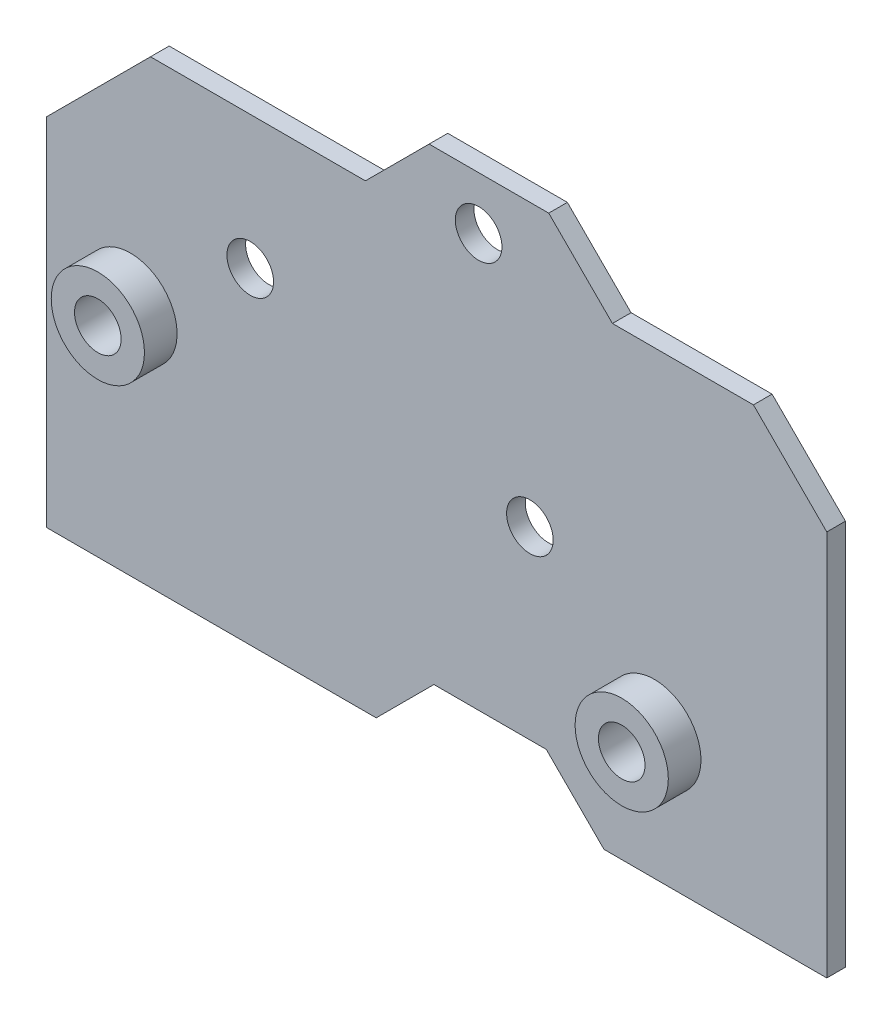
SolidWorks part; units mm, degrees
ref_plane "정면" through (0, 0, 0) normal (0, 0, 1) x (1, 0, 0)
ref_plane "윗면" through (0, 0, 0) normal (0, 1, 0) x (1, 0, 0)
ref_plane "우측면" through (0, 0, 0) normal (1, 0, 0) x (0, 0, -1)
sketch "스케치1" plane through (0, 0, 0) normal (0, 0, 1) x (1, 0, 0)
  line L0 (-6.4864, -27.5) -> (-0.2943, -21.3078)
  line L1 (-0.8119, 28.6459) -> (12.021, 28.6459)
  line L2 (-41.8494, 10.661) -> (-41.8494, -27.5)
  line L3 (-41.8494, -27.5) -> (-6.4864, -27.5)
  line L4 (41.8494, 13.9419) -> (41.8494, -27.5)
  line L5 (-0.2943, -21.3078) -> (11.7564, -21.3078)
  line L6 (11.7564, -21.3078) -> (17.9485, -27.5)
  line L7 (17.9485, -27.5) -> (41.8494, -27.5)
  line L8 (-30.6986, 21.8119) -> (-41.8494, 10.661)
  line L9 (33.9795, 21.8119) -> (41.8494, 13.9419)
  line L10 (-0.8119, 28.6459) -> (-7.6458, 21.8119)
  line L11 (-7.6458, 21.8119) -> (-30.6986, 21.8119)
  line L12 (12.021, 28.6459) -> (18.8549, 21.8119)
  line L13 (18.8549, 21.8119) -> (33.9795, 21.8119)
  circle A0 centre (-20, 7.5) radius 2.5
  circle A1 centre (4.5, 23) radius 2.5
  circle A2 centre (10, -1.5) radius 2.5
  point P0 (0, 0)
  dimension "D3" = 5
  dimension "D6" = 5
  dimension "D7" = 5
  dimension "D5" = 9
  dimension "D8" = 24.5
  dimension "D9" = 15.5
  dimension "D10" = 24.5
  dimension "D11" = 30
extrude "보스-돌출1" add sketch "스케치1" along normal blind 2
sketch "스케치2" plane through (0, 0, 2) normal (0, 0, 1) x (1, 0, 0)
  line L0 (-41.8494, 10.661) -> (-41.8494, -27.5) construction
  line L1 (-41.8494, -27.5) -> (-6.4864, -27.5) construction
  line L2 (41.8494, -27.5) -> (41.8494, 13.9419) construction
  line L3 (17.9485, -27.5) -> (41.8494, -27.5) construction
  circle A0 centre (-32.8494, -2.5) radius 2.5
  circle A1 centre (-32.8494, -2.5) radius 5
  circle A2 centre (23.3494, -14) radius 5
  circle A3 centre (23.3494, -14) radius 2.5
  dimension "D1" = 10
  dimension "D2" = 5
  dimension "D5" = 10
  dimension "D6" = 5
  dimension "D3" = 9
  dimension "D4" = 25
  dimension "D7" = 18.5
  dimension "D8" = 13.5
extrude "보스-돌출3" add sketch "스케치2" along normal blind 3.5
extrude "컷-돌출1" cut sketch "스케치2<2>" against normal up to next contours A0 | A3
sketch "스케치2<2>" plane through (0, 0, 2) normal (0, 0, 1) x (1, 0, 0) same geometry as "스케치2"
